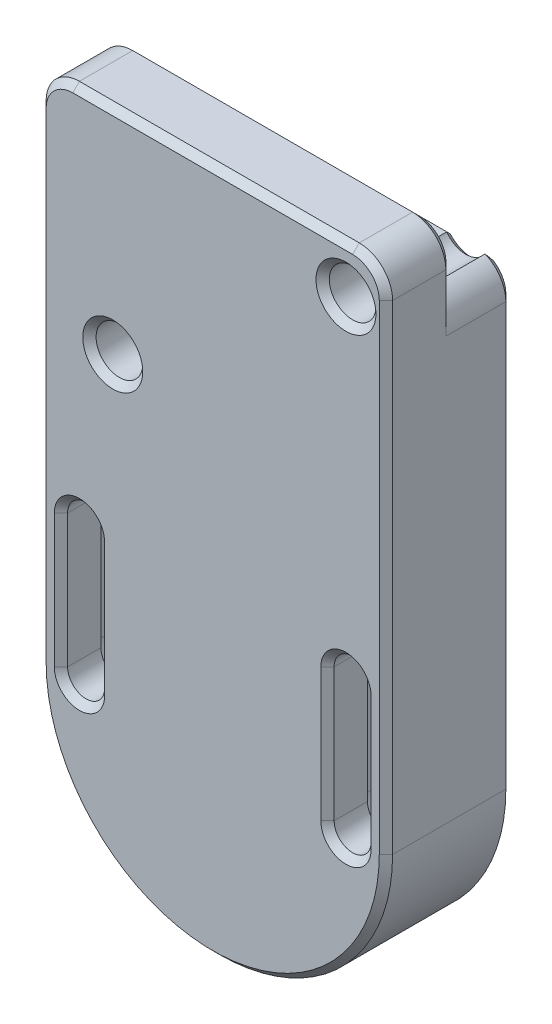
SolidWorks part; units mm, degrees
other "Markup1"
sketch "Sketch6" plane through (209, -32, 19) normal (-0.4079, -0.0172, 0.9129) x (0.0864, -0.9961, 0.0199)
ref_plane "Front Plane" through (0, 0, 0) normal (0, 0, 1) x (1, 0, 0)
ref_plane "Top Plane" through (0, 0, 0) normal (0, 1, 0) x (1, 0, 0)
ref_plane "Right Plane" through (0, 0, 0) normal (1, 0, 0) x (0, 0, -1)
sketch "Sketch1" plane through (0, 0, 0) normal (0, 0, 1) x (1, 0, 0)
  line L0 (210, 74) -> (300, 74) construction
  line L1 (210, 300) -> (210, 74) construction
  line L2 (210, 74) -> (300, 74)
  line L3 (210, 300) -> (210, 74)
  line L4 (261, 71) -> (260, 71)
  line L5 (255, 71) -> (210, 71)
  line L6 (209, 71) -> (209, 41)
  line L7 (209, 41) -> (209, -59)
  line L8 (210, -59) -> (260, -59)
  line L9 (255, 71) -> (260, 71)
  line L10 (261, 71) -> (261, -59)
  line L11 (210, 71) -> (209, 71)
  line L12 (210, -59) -> (209, -59)
  line L13 (261, -59) -> (260, -59)
  circle A4 centre (255, 64) radius 3.5
  circle A5 centre (220, 39) radius 3.5
extrude "Boss-Extrude1" add sketch "Sketch1" along normal blind 19 contours L10 L9 L5 L6 L7 L8 A5 A4 region at (234.9712, 5.476, 0)
sketch "Sketch2" plane through (0, 0, 19) normal (0, 0, 1) x (1, 0, 0)
  line L0 (209, 71) -> (209, -59) construction
  line L1 (209, -59) -> (261, -59) construction
  line L2 (261, 71) -> (261, -59) construction
  line L4 (209, -59) -> (261, -59)
  line L6 (209, -6) -> (209, -59)
  line L7 (261, -6) -> (261, -59)
  arc A0 (209, -6) -> (261, -6) centre (235, -6) ccw
extrude "Cut-Extrude1" cut sketch "Sketch2" against normal through all
sketch "Sketch3" plane through (0, 0, 19) normal (0, 0, 1) x (1, 0, 0)
  line L4 (212.225, 14) -> (212.225, -6)
  line L5 (217.775, 14) -> (217.775, -6)
  line L6 (252.225, 14) -> (252.225, -6)
  line L7 (257.775, 14) -> (257.775, -6)
  arc A0 (252.225, -6) -> (257.775, -6) centre (255, -6) ccw
  arc A6 (212.225, -6) -> (217.775, -6) centre (215, -6) ccw
  arc A7 (217.775, 14) -> (212.225, 14) centre (215, 14) ccw
  arc A8 (257.775, 14) -> (252.225, 14) centre (255, 14) ccw
extrude "Cut-Extrude2" cut sketch "Sketch3" against normal through all
sketch "Sketch4" plane through (0, 0, 0) normal (0, 0, -1) x (-1, 0, 0)
  line L0 (-251, 14) -> (-251, -6)
  line L1 (-259, 14) -> (-259, -6)
  line L2 (-219, 14) -> (-219, -6)
  line L3 (-211, 14) -> (-211, -6)
  arc A0 (-251, 14) -> (-259, 14) centre (-255, 14) ccw
  arc A1 (-259, -6) -> (-251, -6) centre (-255, -6) ccw
  arc A2 (-219, -6) -> (-211, -6) centre (-215, -6) ccw
  arc A3 (-211, 14) -> (-219, 14) centre (-215, 14) ccw
extrude "Cut-Extrude3" cut sketch "Sketch4" against normal offset from surface (13 mm away) 6 up to face at (255, 4, 19)
sketch "Sketch5" plane through (261, 0, 0) normal (1, 0, 0) x (0, 0, -1)
  line L1 (0, 71) -> (-9, 71)
  line L2 (0, 71) -> (0, 62)
  line L3 (0, 62) -> (-9, 62)
  line L4 (-9, 71) -> (-9, 62)
extrude "Cut-Extrude4" cut sketch "Sketch5" against normal through all
fillet "Fillet1" radius 5 4 edges at (209, 71, 14) (261, 71, 14) (209, 62, 4.5) (261, 62, 4.5)
chamfer "Chamfer1" distance 1 angle 45 37 edges at (235, -32, 0) (261, 25.6819, 0) (209, 25.5, 0) (255, 60.5, 0) (223.5, 39, 0) (215, -10, 0) (211, 4, 0) (215, 18, 0) (219, 4, 0) (255, -10, 0) (251, 4, 0) (255, 18, 0) (259, 4, 0) (258.5, 64, 19) (223.5, 39, 19) (259.5355, 69.5355, 19) (261, 30, 19) (235, -32, 19) (209, 30, 19) (210.4645, 69.5355, 19) (235, 71, 19) (233.0639, 62, 0) (209, 61.5, 9) (261, 61.6819, 9) (210.4645, 69.5355, 9) (259.5355, 69.5355, 9) (235, 71, 9) (260.145, 60.1601, 0) (210.4645, 60.5355, 0) (212.225, 4, 19) (215, -8.775, 19) (217.775, 4, 19) (215, 16.775, 19) (252.225, 4, 19) (255, -8.775, 19) (257.775, 4, 19) (255, 16.775, 19)
